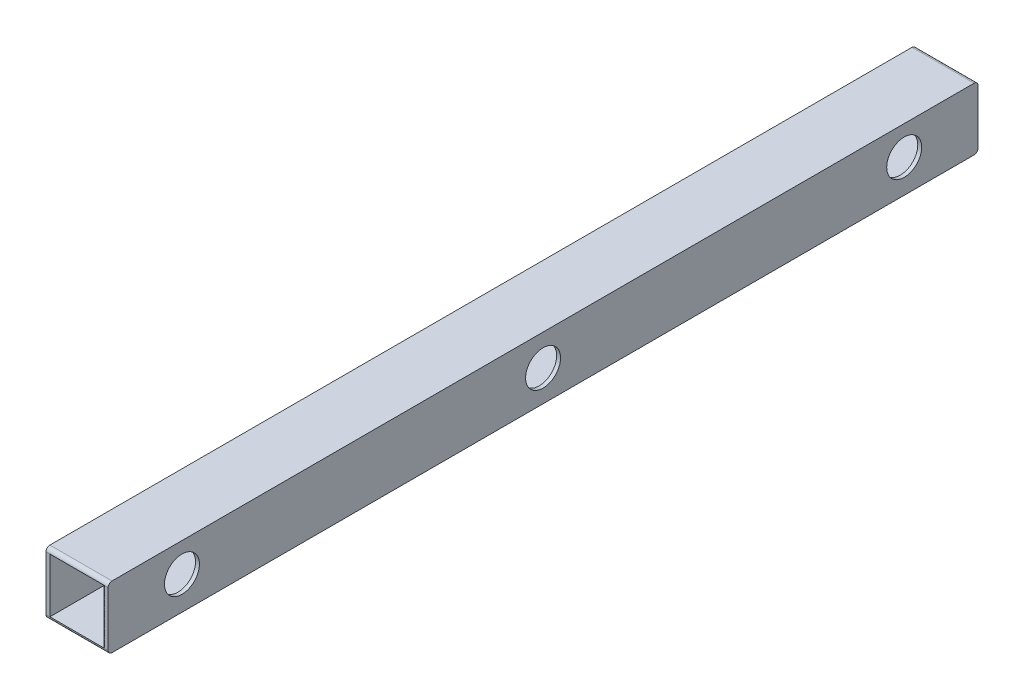
SolidWorks part; units mm, degrees
material "6061-T6 (SS)"
ref_plane "Front Plane" through (0, 0, 0) normal (0, 0, 1) x (1, 0, 0)
ref_plane "Top Plane" through (0, 0, 0) normal (0, 1, 0) x (1, 0, 0)
ref_plane "Right Plane" through (0, 0, 0) normal (1, 0, 0) x (0, 0, -1)
sketch "Sketch1" plane through (0, 0, 0) normal (0, 0, 1) x (1, 0, 0)
  line L1 (-25.4, -25.4) -> (25.4, -25.4)
  line L2 (-25.4, -25.4) -> (-25.4, 25.4)
  line L3 (-25.4, 25.4) -> (25.4, 25.4)
  line L4 (25.4, -25.4) -> (25.4, 25.4)
  line L5 (-25.4, -25.4) -> (25.4, 25.4) construction
  line L6 (-25.4, 25.4) -> (25.4, -25.4) construction
  line L7 (-22.225, -22.225) -> (22.225, -22.225)
  line L8 (-22.225, -22.225) -> (-22.225, 22.225)
  line L9 (-22.225, 22.225) -> (22.225, 22.225)
  line L10 (22.225, -22.225) -> (22.225, 22.225)
  line L11 (-22.225, -22.225) -> (22.225, 22.225) construction
  line L12 (-22.225, 22.225) -> (22.225, -22.225) construction
  point P0 (0, 0)
  point P6 (0, 0)
  dimension "D1" = 3.175
  dimension "D2" = 3.175
  dimension "D3" = 50.8
extrude "Boss-Extrude1" add sketch "Sketch1" along normal blind 355.6 and the other way blind 355.6
sketch "Sketch2" plane through (-25.4, 0, 0) normal (-1, 0, 0) x (0, 0, 1)
  line L0 (-355.6, 0) -> (355.6, 0) construction
  line L1 (-355.6, 25.4) -> (-355.6, -25.4) construction
  line L2 (355.6, 25.4) -> (355.6, -25.4) construction
  line L3 (0, -25.4) -> (0, 25.4) construction
  line L4 (-355.6, -25.4) -> (355.6, -25.4) construction
  line L5 (-355.6, 25.4) -> (355.6, 25.4) construction
  line L6 (0, -0.7937) -> (-295.2404, 1.5875) construction
  line L7 (-0.1412, -18.3002) -> (-295.3816, -15.919) construction
  line L8 (0.1412, 16.7127) -> (-295.0992, 19.094) construction
  circle A0 centre (-295.2404, 1.5875) radius 14.2875
  arc A1 (-0.1412, -18.3002) -> (0.1412, 16.7127) centre (0, -0.7937) ccw construction
  arc A2 (-295.0992, 19.094) -> (-295.3816, -15.919) centre (-295.2404, 1.5875) ccw construction
  circle A3 centre (0, 0) radius 14.2875
  circle A4 centre (295.2404, 1.5875) radius 14.2875
  point P14 (-147.6202, 0.3969)
  dimension "D1" = 17.507
  dimension "D3" = 700.5
  dimension "D5" = 28.575
  dimension "D2" = 0.7937
  dimension "D4" = 1.5875
extrude "Cut-Extrude1" cut sketch "Sketch2" against normal through all
fillet "Fillet1" radius 3.175 4 edges at (0, 25.4, 355.6) (0, -25.4, 355.6) (0, -25.4, -355.6) (0, 25.4, -355.6)
equation "\"D1@Sketch2\"=22*5mm/pi/2"
equation "\"D3@Sketch2\"=140*5mm+.5mm"
